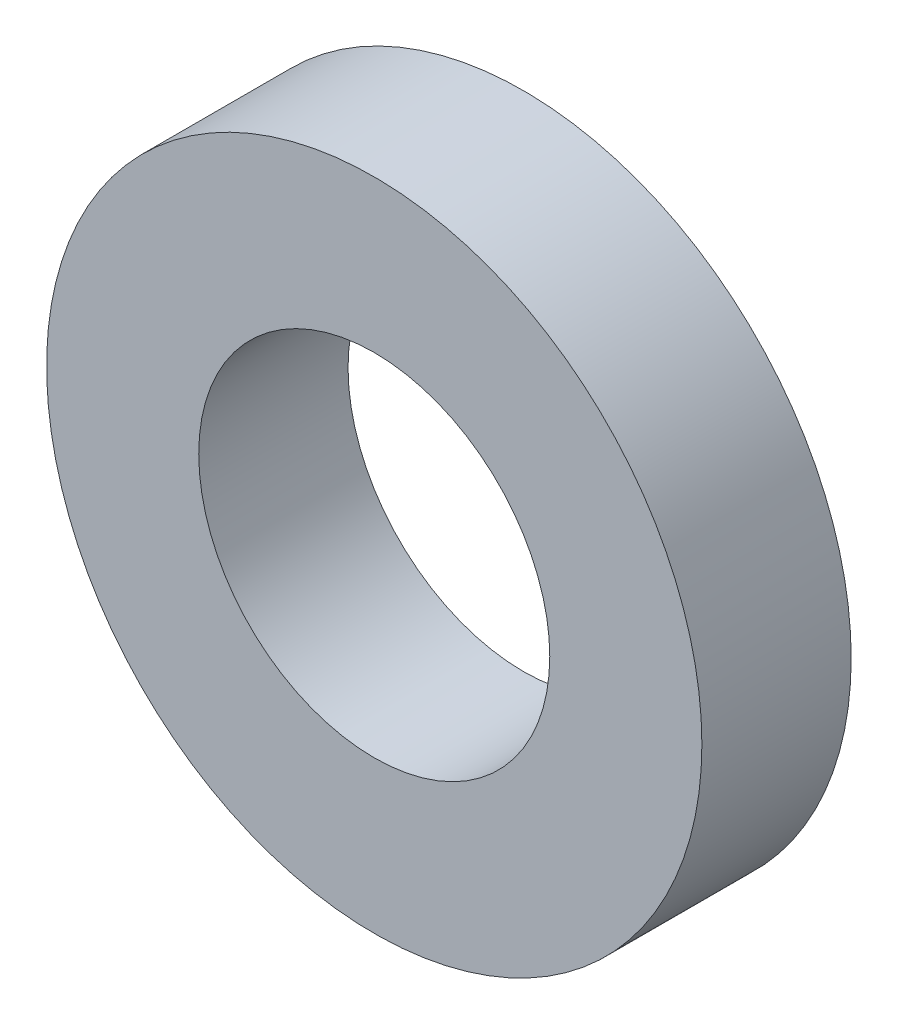
SolidWorks part; units mm, degrees
material "PET"
ref_plane "Front Plane" through (0, 0, 0) normal (0, 0, 1) x (1, 0, 0)
ref_plane "Top Plane" through (0, 0, 0) normal (0, 1, 0) x (1, 0, 0)
ref_plane "Right Plane" through (0, 0, 0) normal (1, 0, 0) x (0, 0, -1)
sketch "Sketch1" plane through (0, 0, 0) normal (0, 0, 1) x (1, 0, 0)
  circle A0 centre (0, 0) radius 4.7625
  circle A1 centre (0, 0) radius 8.89
  dimension "D1" = 9.525
  dimension "D2" = 17.78
extrude "Boss-Extrude1" add sketch "Sketch1" along normal mid plane 4.0513
